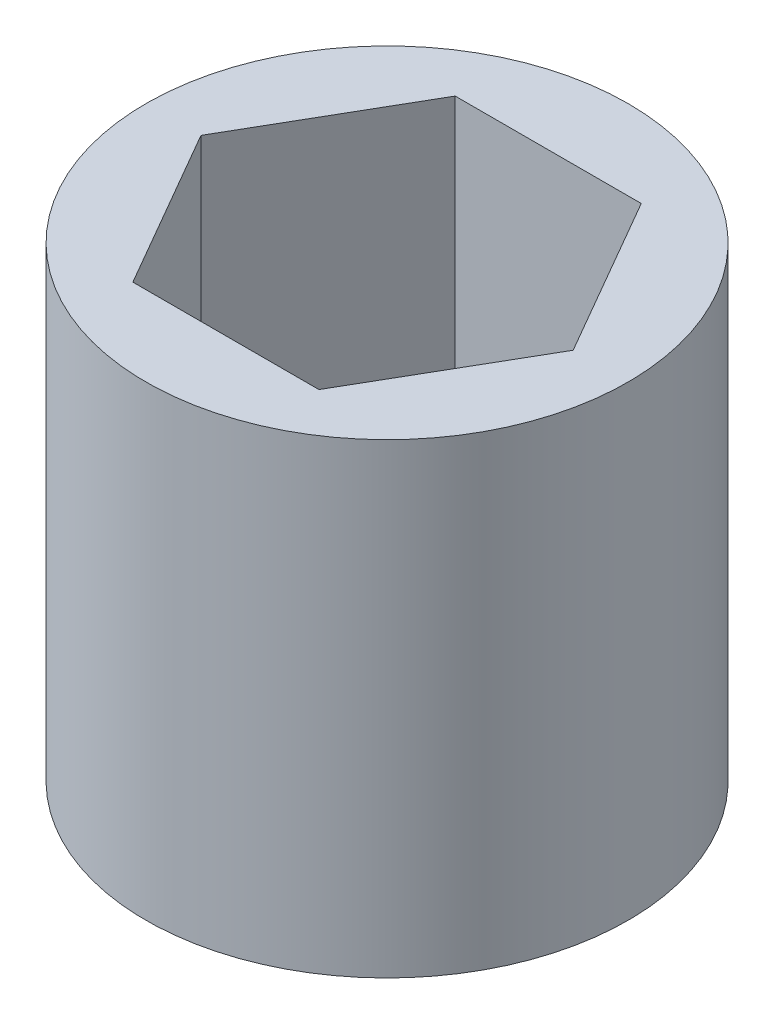
SolidWorks part; units mm, degrees
ref_plane "Front Plane" through (0, 0, 0) normal (0, 0, 1) x (1, 0, 0)
ref_plane "Top Plane" through (0, 0, 0) normal (0, 1, 0) x (1, 0, 0)
ref_plane "Right Plane" through (0, 0, 0) normal (1, 0, 0) x (0, 0, -1)
sketch "Sketch1" plane through (0, 0, 0) normal (0, 1, 0) x (1, 0, 0)
  line L0 (-2.894, -5.0125) -> (2.894, -5.0125)
  line L1 (2.894, -5.0125) -> (5.7879, 0)
  line L2 (5.7879, 0) -> (2.894, 5.0125)
  line L3 (2.894, 5.0125) -> (-2.894, 5.0125)
  line L4 (-2.894, 5.0125) -> (-5.7879, 0)
  line L5 (-5.7879, 0) -> (-2.894, -5.0125)
  circle A0 centre (0, 0) radius 7.5
  point P7 (0, 0)
  point P9 (0, 5.0125)
  dimension "D3" = 15
  dimension "D1" = 120
  dimension "D2" = 10.025
extrude "Boss-Extrude1" add sketch "Sketch1" along normal mid plane 14.5
ref_axis "Axis1" through (0, 0, 0) along (0, 1, 0)
